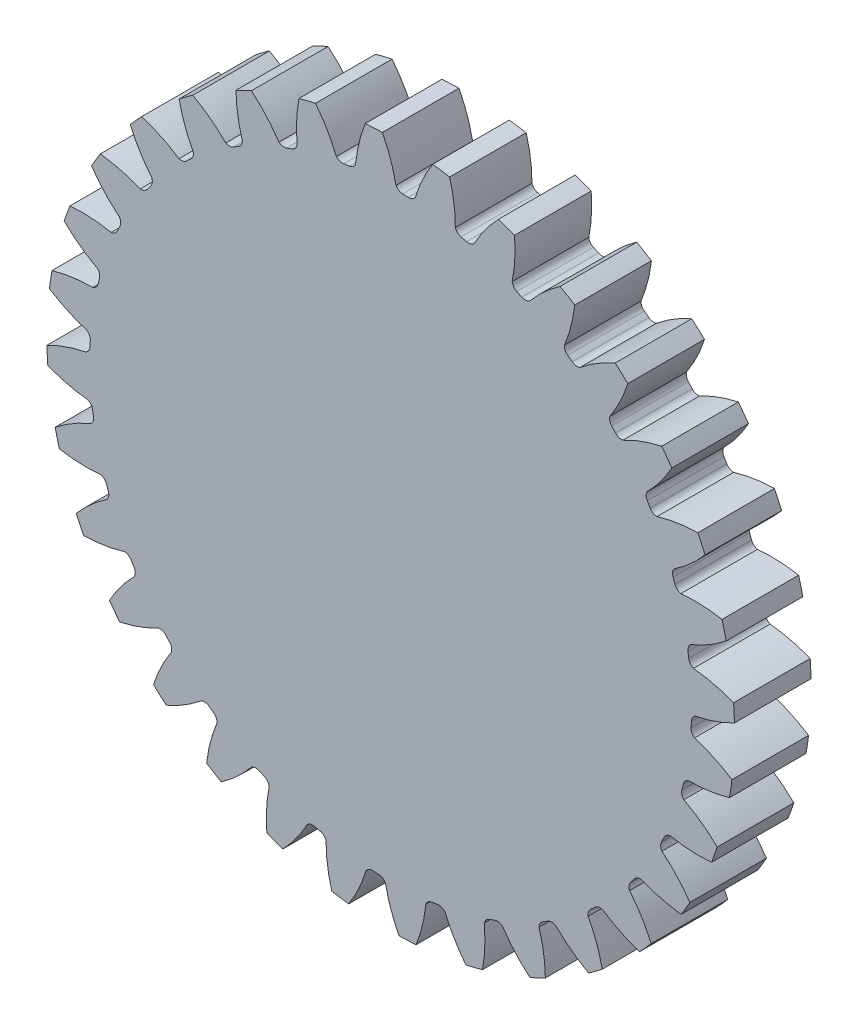
SolidWorks part; units mm, degrees
ref_plane "Front" through (0, 0, 0) normal (0, 0, 1) x (1, 0, 0)
ref_plane "Top" through (0, 0, 0) normal (0, 1, 0) x (1, 0, 0)
ref_plane "Right" through (0, 0, 0) normal (1, 0, 0) x (0, 0, -1)
sketch "Sketch1" plane through (0, 0, 0) normal (0, 0, 1) x (1, 0, 0)
  line L0 (-406.4, 0) -> (406.4, 0) construction
  circle A0 centre (0, 0) radius 13.462
  circle A1 centre (0, 0) radius 12.7 construction
  circle A3 centre (0, 0) radius 11.7816 construction
  dimension "D1" = 0.9184
  dimension "D2" = 1.6804
extrude "Boss-Extrude1" add sketch "Sketch1" against normal blind 3
sketch "Sketch3" plane through (0, 0, 0) normal (0, 0, 1) x (1, 0, 0)
  line L0 (0, 0) -> (0, 13.462) construction
  line L1 (-4.0817, 11.2144) -> (0, 12.7)
  line L2 (-9.5921, 12.7) -> (9.5921, 12.7) construction
  line L3 (-9.0136, 9.4193) -> (9.0136, 15.9807) construction
  line L4 (-4.0817, 11.2144) -> (0, 0) construction
  line L5 (-8.5944, 8.28) -> (0, 0) construction
  line L6 (-8.5944, 8.28) -> (-1.8137, 15.3183) construction
  line L7 (-2.8353, 11.5924) -> (0, 0) construction
  line L8 (-2.8353, 11.5924) -> (0.1182, 12.3148) construction
  arc A0 (-4.0817, 11.2144) -> (-8.5944, 8.28) centre (0, 0) ccw
  circle A1 centre (0, 0) radius 12.7 construction
  circle A2 centre (0, 0) radius 11.9341 construction
  arc A3 (-4.0817, 11.2144) -> (-2.8353, 11.5924) centre (0, 0) cw
  circle A4 centre (0, 0) radius 13.462 construction
  point P6 (0, 12.7)
  dimension "D1" = 4.3437
  dimension "D3" = 9.7732
  dimension "D5" = 3.0406
  dimension "D2" = 5.4296
  dimension "D4" = 1.3031
sketch "Sketch4" plane through (0, 0, 0) normal (0, 0, 1) x (1, 0, 0)
  line L0 (0, 0) -> (0.6224, 12.6694) construction
  line L1 (0.2075, 11.9323) -> (0.2075, 11.7798)
  line L2 (0, 12.7) -> (1.2448, 12.6388) construction
  line L3 (0.9631, 11.8952) -> (0.9482, 11.7434)
  line L4 (0.2075, 11.7798) -> (0, 0) construction
  line L5 (0, 0) -> (0, 13.462) construction
  line L6 (-8.5944, 8.28) -> (-1.8137, 15.3183) construction
  line L7 (-8.5944, 8.28) -> (-1.8137, 15.3183) construction
  arc A0 (0.9482, 11.7434) -> (0.2075, 11.7798) centre (0, 0) ccw
  arc A1 (0, 12.7) -> (1.2448, 12.6388) centre (0, 0) cw construction
  circle A2 centre (0, 0) radius 12.7 construction
  circle A3 centre (0, 0) radius 11.9341 construction
  circle A4 centre (0, 0) radius 11.7816 construction
  arc A5 (3.3064, 15.0667) -> (-1.8137, 15.3183) centre (0, 0) ccw
  spline S0 degree 2 poles (-1.8137, 15.3183) (-0.1814, 13.8884) (0.2075, 11.9323) knots 0 0 0 1 1 1
  spline S1 degree 2 poles (3.3064, 15.0667) (1.5418, 13.8038) (0.9631, 11.8952) knots 0 0 0 1 1 1
  dimension "D1" = 1.2468
extrude "Cut-Extrude1" cut sketch "Sketch4" against normal through all
fillet "Fillet1" radius 0.3117 2 edges at (0.9482, 11.7434, -1.5) (0.2075, 11.7798, -1.5)
pattern_circular "CirPattern1" count 32 over 360 about axis through (0, 0, -3) along (0, 0, 1) of "Cut-Extrude1", "Fillet1"
sketch "Pitch Dia" plane through (0, 0, 0) normal (0, 0, 1) x (1, 0, 0)
  circle A0 centre (0, 0) radius 12.7 construction
  circle A1 centre (0, 0) radius 12.7
equation "\"D2@Sketch3\" = \"D1@Sketch3\"*1.25"
equation "\"D3@Sketch3\" = \"D1@Sketch3\"+\"D2@Sketch3\""
equation "\"D4@Sketch3\" = \"D1@Sketch3\"*.3"
equation "\"D5@Sketch3\" = \"D1@Sketch3\"-\"D4@Sketch3\""
equation "\"D1@Sketch4\" = 1.5708/(\"Number of Teeth@Sketch1\"/\"Pitch Diameter@Sketch1\")"
equation "\"D1@CirPattern1\" = \"Number of Teeth@Sketch1\""
equation "\"D1@Fillet1\" = \"D1@Sketch4\"*.25"
equation "\"D1@Sketch1\" = 1.157/(\"Number of Teeth@Sketch1\"/\"Pitch Diameter@Sketch1\")"
